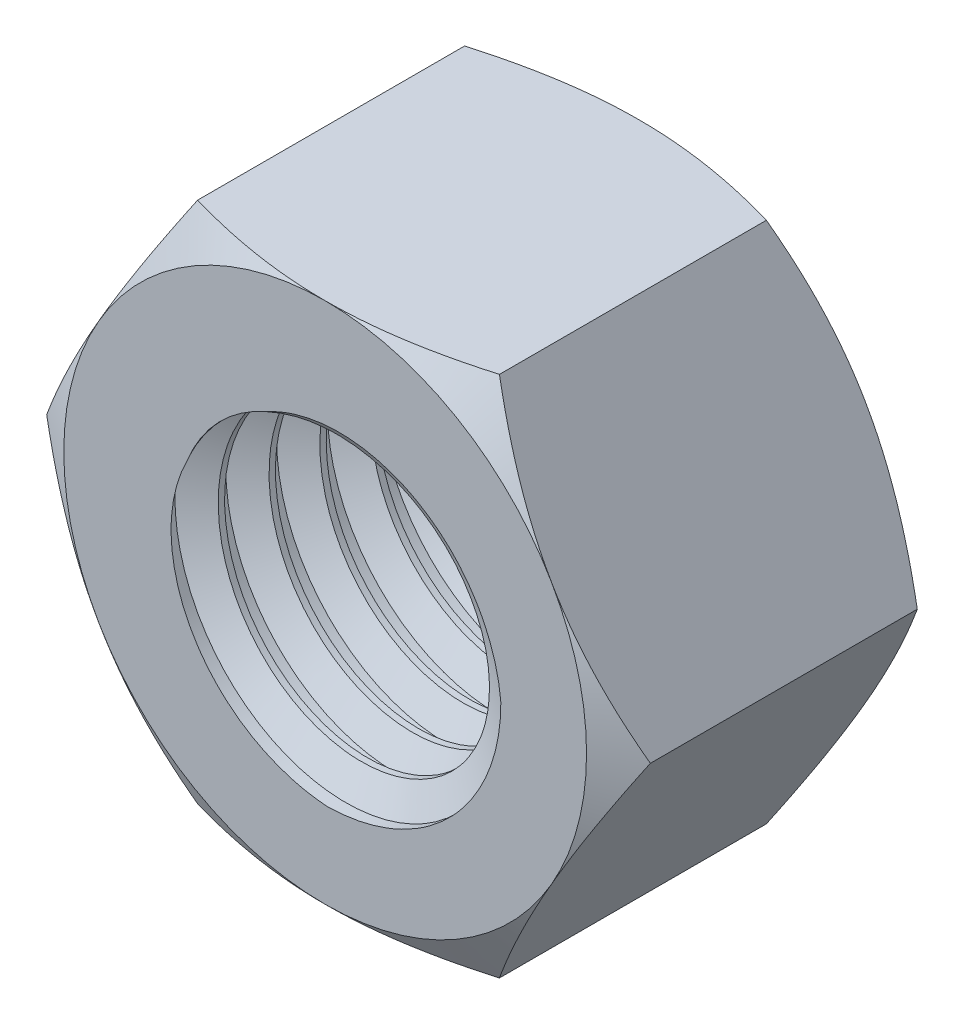
SolidWorks part; units mm, degrees
ref_plane "Front Plane" through (0, 0, 0) normal (0, 0, 1) x (1, 0, 0)
ref_plane "Top Plane" through (0, 0, 0) normal (0, 1, 0) x (1, 0, 0)
ref_plane "Right Plane" through (0, 0, 0) normal (1, 0, 0) x (0, 0, -1)
sketch "Sketch1" plane through (0, 0, 0) normal (0, 0, 1) x (1, 0, 0)
  line L1 (5.1962, 9) -> (-5.1962, 9)
  line L2 (-5.1962, 9) -> (-10.3923, 0)
  line L3 (-10.3923, 0) -> (-5.1962, -9)
  line L4 (-5.1962, -9) -> (5.1962, -9)
  line L5 (5.1962, -9) -> (10.3923, 0)
  line L6 (10.3923, 0) -> (5.1962, 9)
  circle A0 centre (0, 0) radius 9 construction
  dimension "D1" = 18
extrude "Boss-Extrude1" add sketch "Sketch1" along normal blind 10.8
sketch "Sketch3" plane through (0, 0, 0) normal (1, 0, 0) x (0, 0, -1)
  line L0 (0, 9) -> (0, 11.8226)
  line L1 (0, 11.8226) -> (-1.6297, 11.8226)
  line L2 (-1.6297, 11.8226) -> (0, 9)
  line L3 (0, 0) -> (50000, 0) construction
  dimension "D1" = 30
revolve "Cut-Revolve1" cut sketch "Sketch3" angle 360 about L3
ref_plane "Plane1" through (0, 0, 5.4) normal (0, 0, -1) x (-1, 0, 0)
mirror "Mirror1" about plane through (0, 0, 5.4) normal (0, 0, -1) of "Cut-Revolve1"
hole_wizard "M12x1.75 Tapped Hole1" positions "Sketch6" profile "Sketch7" tap size "M12x1.75" standard "ANSI Metric" end condition through all
sketch "Sketch6" plane through (0, 0, 0) normal (0, 0, -1) x (-1, 0, 0)
  point P0 (0, 0)
sketch "Sketch7" plane through (0, 0, 0) normal (1, 0, 0) x (0, 1, 0)
  line L0 (0, 0) -> (0, 10.8)
  line L1 (0, 10.8) -> (5.1, 10.8)
  line L2 (5.1, 10.8) -> (5.1, 0)
  line L5 (5.1, 0) -> (0, 0)
  line L11 (0, -6.35) -> (0, 107.95) construction
  dimension "Thru Tap Drill Dia." = 10.2
  dimension "Thru Tap Drill Depth" = 10.8
cosmetic thread "Hole Thread1" parameters "D2"=12
thread "Thread1" pitch 1.75 method cut profile "Thread Profile1" start angle 0, offset 2, length 20, pitch 1.75, diameter 10.2
ref_plane "Plane2" through (5.1, 0, -2) normal (0, 1, 0) x (-1, 0, 0)
sketch "Thread Profile1" plane through (5.1, 0, -2) normal (0, 1, 0) x (-1, 0, 0)
  line L0 (0, 0) -> (0, 1.75) construction
  line L11 (0, 0) -> (0, 1.5312)
  line L12 (0, 1.5312) -> (-0.9472, 0.9844)
  line L13 (-0.9472, 0.9844) -> (-0.9472, 0.5469)
  line L15 (-0.9472, 0.5469) -> (0, 0)
  line L17 (-0.9472, 0.7656) -> (0, 0.7656) construction
  point P2 (0, 0)
  dimension "Pitch" = 1.75
  dimension "Profile_Angle" = 60
  dimension "Profile_Land" = 0.4375
  dimension "Profile_Height" = 0.9472
